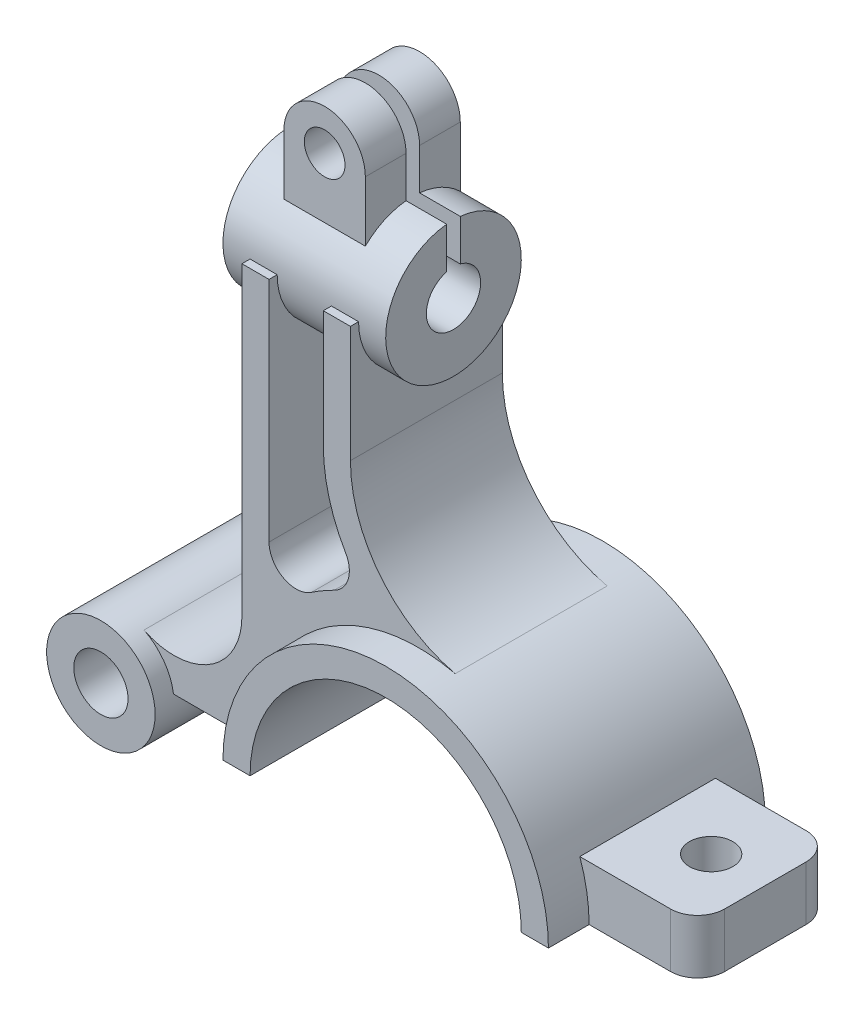
SolidWorks part; units mm, degrees
ref_plane "Front Plane" through (0, 0, 0) normal (0, 0, 1) x (1, 0, 0)
ref_plane "Top Plane" through (0, 0, 0) normal (0, 1, 0) x (1, 0, 0)
ref_plane "Right Plane" through (0, 0, 0) normal (1, 0, 0) x (0, 0, -1)
sketch "Sketch1" plane through (0, 0, 0) normal (0, 0, 1) x (1, 0, 0)
  line L0 (-60, 0) -> (60, 0) construction
  arc A0 (60, 0) -> (-60, 0) centre (0, 0) ccw
  dimension "D1" = 60
extrude "Extrude-Thin1" add sketch "Sketch1" along normal mid plane 80 thin thin type one direction reverse wall 10
sketch "Sketch2" plane through (0, 0, 0) normal (0, 0, 1) x (1, 0, 0)
  circle A0 centre (-110, -2.9292) radius 20
  dimension "D2" = 40
  dimension "D1" = 110
extrude "Extrude-Thin2" add sketch "Sketch2" along normal mid plane 70 separate body thin thin type one direction reverse wall 10
sketch "Sketch3" plane through (0, 0, 0) normal (0, -1, 0) x (1, 0, 0)
  line L1 (100, 25) -> (0, 25)
  line L2 (100, 25) -> (100, -25)
  line L3 (100, -25) -> (0, -25)
  line L4 (0, 25) -> (0, -25)
  dimension "D1" = 100
  dimension "D2" = 50
extrude "Boss-Extrude1" add sketch "Sketch3" against normal blind 20
other "DeleteFace4" face at (22.9129, 20, 0) face at (24.2145, 10.0539, -25) face at (24.2145, 10.0539, 25) face at (0, 10, 0) and patch yes
fillet "Fillet1" radius 10 2 edges at (100, 10, -25) (100, 10, 25)
sketch "Sketch4" plane through (0, 20, 0) normal (0, 1, 0) x (1, 0, 0)
  line L0 (100, 15) -> (100, -15) construction
  point P0 (80, 0)
  dimension "D1" = 20
hole_wizard "Ø16.0 (16) Diameter Hole1" positions "Sketch4" profile "Sketch5" hole size "Ø16.0" standard "ANSI Metric" end condition through all
sketch "Sketch5" plane through (80, 20, 0) normal (1, 0, 0) x (0, 0, 1)
  line L0 (0, 0) -> (0, 42.9292)
  line L1 (0, 42.9292) -> (8, 42.9292)
  line L2 (8, 42.9292) -> (8, 0)
  line L5 (8, 0) -> (0, 0)
  line L11 (0, -6.35) -> (0, 107.95) construction
  dimension "Thru Hole Dia." = 16
  dimension "Thru Hole Depth" = 42.9292
ref_plane "Plane1" through (-15, 0, 0) normal (1, 0, 0) x (0, 0, -1)
sketch "Sketch6" plane through (-15, 0, 0) normal (1, 0, 0) x (0, 0, -1)
  circle A0 centre (0, 150) radius 25
  dimension "D1" = 50
  dimension "D2" = 150
extrude "Boss-Extrude2" add sketch "Sketch6" against normal blind 60 separate body
sketch "Sketch7" plane through (0, 0, 0) normal (0, 0, 1) x (1, 0, 0)
  line L0 (-75, 150) -> (-15, 150) construction
  line L1 (-75, 175) -> (-75, 125) construction
  line L2 (-15, 125) -> (-15, 175) construction
  line L3 (-60, 150) -> (-60, 190)
  line L4 (-30, 190) -> (-30, 150)
  line L5 (-30, 150) -> (-60, 150)
  line L6 (-45, 150) -> (-45, 219.4262) construction
  arc A0 (-60, 190) -> (-30, 190) centre (-45, 190) cw
  circle A1 centre (-45, 190) radius 7.5
  point P12 (0, 0)
  point P13 (-45, 219.4262)
  point P16 (0, 0)
  dimension "D1" = 15
  dimension "D2" = 15
  dimension "D3" = 40
extrude "Boss-Extrude3" add sketch "Sketch7" along normal mid plane 35
sketch "Sketch8" plane through (0, 0, 0) normal (0, 0, 1) x (1, 0, 0)
  line L0 (-75, 150) -> (-15, 150) construction
  line L1 (-75, 175) -> (-75, 125) construction
  line L2 (-15, 125) -> (-15, 175) construction
  line L3 (-25, 150) -> (-25, 107.1214)
  line L4 (-65, 150) -> (-65, 37.3821)
  line L5 (-35, 150) -> (-35, 107.1214)
  line L6 (-55, 150) -> (-55, 66.1438)
  line L7 (-55, 150) -> (-55, 37.3821) construction
  line L8 (-60, 0) -> (-90.2157, 0)
  line L10 (-65, 150) -> (-55, 150)
  line L11 (-35, 150) -> (-25, 150)
  arc A0 (-25, 107.1214) -> (13.6364, 58.4299) centre (25, 107.1214) ccw
  arc A1 (60, 0) -> (-60, 0) centre (0, 0) ccw construction
  arc A2 (-65, 37.3821) -> (-101.1111, 14.987) centre (-90, 37.3821) cw
  circle A3 centre (-110, -2.9292) radius 20 construction
  arc A4 (-35, 107.1214) -> (-26.772, 76.7955) centre (25, 107.1214) ccw
  arc A6 (-55, 37.3821) -> (-105.5556, 6.0289) centre (-90, 37.3821) cw construction
  arc A7 (-35, 107.1214) -> (11.3636, 48.6916) centre (25, 107.1214) ccw construction
  arc A8 (70, 0) -> (-70, 0) centre (0, 0) ccw
  arc A9 (-30.9756, 62.7735) -> (-39.375, 57.8758) centre (0, 0) ccw
  arc A10 (-90.2157, 0) -> (-101.1111, 14.987) centre (-110, -2.9292) ccw
  arc A11 (13.6364, 58.4299) -> (-60, 0) centre (0, 0) ccw
  arc A12 (-30.9756, 62.7735) -> (-26.772, 76.7955) centre (-35.4006, 71.7412) ccw
  arc A13 (-39.375, 57.8758) -> (-55, 66.1438) centre (-45, 66.1438) cw
  dimension "D1" = 50
  dimension "D2" = 25
  dimension "D8" = 10
  dimension "D3" = 10
  dimension "D4" = 10
  dimension "D5" = 10
  dimension "D6" = 10
  dimension "D7" = 10
extrude "Boss-Extrude4" add sketch "Sketch8" along normal mid plane 56
sketch "Sketch9" plane through (-15, 0, 0) normal (1, 0, 0) x (0, 0, -1)
  point P0 (0, 150)
hole_wizard "Ø20.0 (20) Diameter Hole1" positions "Sketch9" profile "Sketch10" hole size "Ø20.0" standard "ANSI Metric" end condition through all
sketch "Sketch10" plane through (-15, 150, 0) normal (0, 1, 0) x (0, 0, -1)
  line L0 (0, 0) -> (0, 115)
  line L1 (0, 115) -> (10, 115)
  line L2 (10, 115) -> (10, 0)
  line L5 (10, 0) -> (0, 0)
  line L11 (0, -6.35) -> (0, 107.95) construction
  dimension "Thru Hole Dia." = 20
  dimension "Thru Hole Depth" = 115
sketch "Sketch11" plane through (-15, 0, 0) normal (1, 0, 0) x (0, 0, -1)
  line L0 (0, 150) -> (0, 205)
  line L1 (17.5, 205) -> (-17.5, 205) construction
extrude "Cut-Extrude-Thin1" cut sketch "Sketch11" against normal through all both and the other way through all thin thin type mid plane wall 5
